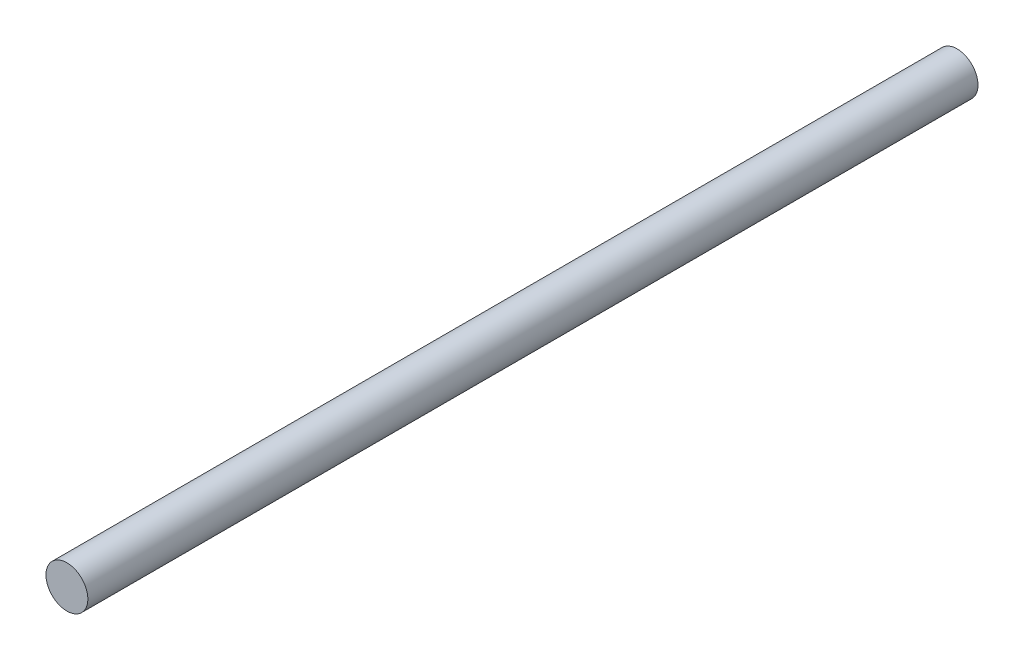
SolidWorks part; units mm, degrees
ref_plane "Front Plane" through (0, 0, 0) normal (0, 0, 1) x (1, 0, 0)
ref_plane "Top Plane" through (0, 0, 0) normal (0, 1, 0) x (1, 0, 0)
ref_plane "Right Plane" through (0, 0, 0) normal (1, 0, 0) x (0, 0, -1)
ref_axis "Axis1" through (0, 0, -7.5) along (0, 0, 1)
sketch "Sketch1" plane through (0, 0, 0) normal (0, 0, 1) x (1, 0, 0)
  circle A0 centre (0, 0) radius 2
  dimension "D1" = 4
extrude "Main" add sketch "Sketch1" along normal blind 85
